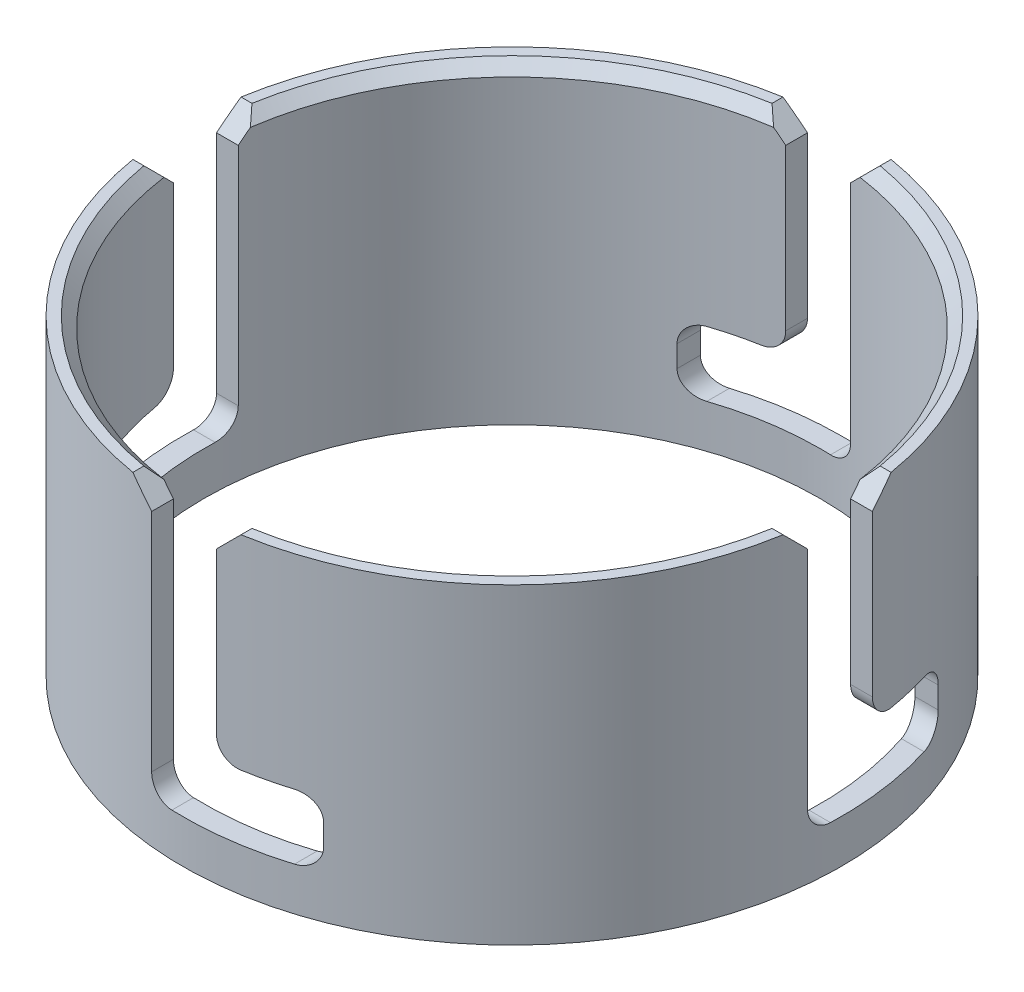
SolidWorks part; units mm, degrees
material "Plain Carbon Steel"
ref_plane "Front Plane" through (0, 0, 0) normal (0, 0, 1) x (1, 0, 0)
ref_plane "Top Plane" through (0, 0, 0) normal (0, 1, 0) x (1, 0, 0)
ref_plane "Right Plane" through (0, 0, 0) normal (1, 0, 0) x (0, 0, -1)
sketch "Sketch2" plane through (0, 0, 0) normal (1, 0, 0) x (0, 0, -1)
  line L0 (-71.2, 0) -> (-76.2, 0)
  line L1 (-76.2, 0) -> (-76.2, 72.15)
  line L2 (-76.2, 72.15) -> (-71.2, 72.15)
  line L5 (-71.2, 72.15) -> (-71.2, 0)
  dimension "D1" = 76.2
  dimension "D2" = 72.15
  dimension "D3" = 5
ref_axis "Axis1" through (0, -3.6075, 0) along (0, 1, 0)
revolve "Revolve1" add sketch "Sketch2" angle 360 about axis through (0, -3.6075, 0) along (0, 1, 0)
sketch "Sketch3" plane through (0, 0, 0) normal (1, 0, 0) x (0, 0, -1)
  line L0 (-7.5, 72.15) -> (7.5, 72.15)
  line L1 (76.2, 72.15) -> (-76.2, 72.15) construction
  line L2 (7.5, 72.15) -> (7.5, 10)
  line L3 (7.5, 10) -> (-27.5, 10)
  line L4 (-27.5, 10) -> (-27.5, 25)
  line L5 (-27.5, 25) -> (-7.5, 25)
  line L6 (-7.5, 25) -> (-7.5, 72.15)
  line L7 (0, -3.6075) -> (0, 75.7575) construction
  line L8 (0, 0) -> (0, 47.5309) construction
  line L9 (-76.2, 0) -> (76.2, 0) construction
  dimension "D1" = 10
  dimension "D2" = 15
  dimension "D3" = 15
  dimension "D4" = 20
extrude "Cut-Extrude1" cut sketch "Sketch3" against normal through all
fillet "Fillet1" radius 5 2 edges at (-73.3169, 25, 7.5) (-73.3169, 10, -7.5)
chamfer "Chamfer1" distance 5 angle 45 2 edges at (-73.3169, 72.15, 7.5) (-73.3169, 72.15, -7.5)
fillet "Fillet3" radius 5 2 edges at (-68.3698, 25, 27.5) (-68.3698, 10, 27.5)
pattern_circular "CirPattern1" count 4 over 360 about axis through (0, -3.6075, 0) along (0, 1, 0) of "Fillet3", "Chamfer1", "Fillet1", "Cut-Extrude1"
chamfer "Chamfer2" distance 2.5 angle 45 4 edges at (-50.346, 72.15, -50.346) (50.346, 72.15, -50.346) (50.346, 72.15, 50.346) (-50.346, 72.15, 50.346)
equation "\"TubeDiameter\" = 6.000in"
equation "\"D1@Sketch2\"=\"TubeDiameter\"/2"
